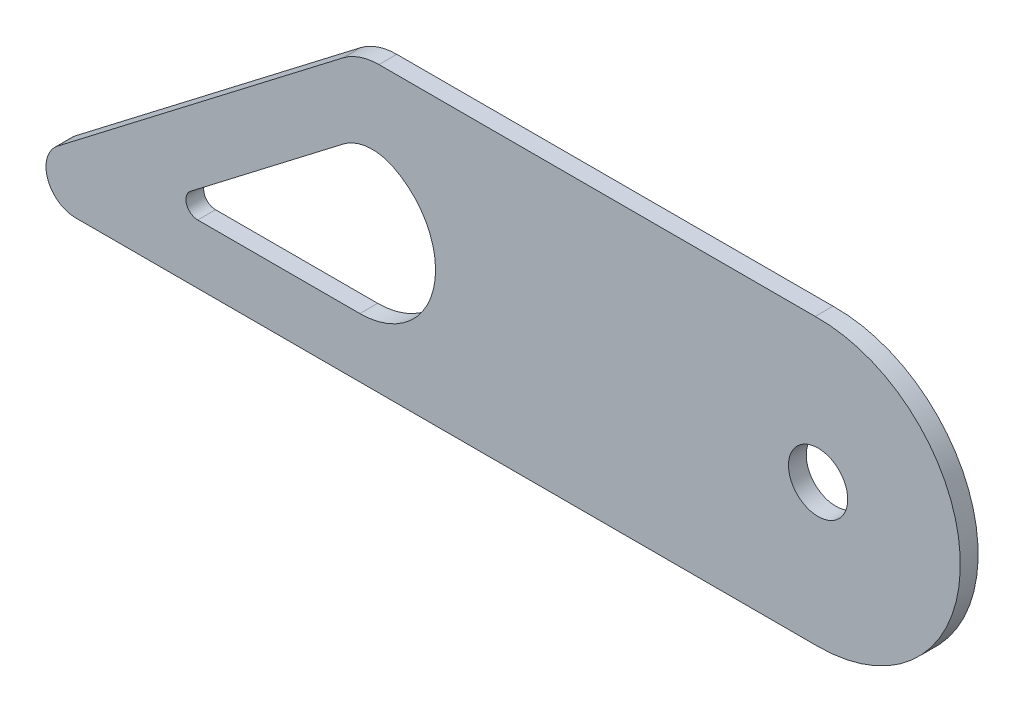
SolidWorks part; units mm, degrees
ref_plane "Front" through (0, 0, 0) normal (0, 0, 1) x (1, 0, 0)
ref_plane "Top" through (0, 0, 0) normal (0, 1, 0) x (1, 0, 0)
ref_plane "Right" through (0, 0, 0) normal (1, 0, 0) x (0, 0, -1)
sketch "Sketch2" plane through (0, 0, 0) normal (0, 0, 1) x (1, 0, 0)
  line L0 (-398.4685, -10.3406) -> (-639.1765, -195.1456)
  line L1 (0, 0) -> (-368.0198, 0)
  line L3 (2.433, -239.9753) -> (-623.9521, -239.9753)
  line L7 (-526.9809, -172.0434) -> (-398.0142, -73.0284)
  line L9 (-384.0981, -189.9753) -> (-520.8912, -189.9753)
  arc A0 (2.433, -239.9753) -> (0, 0) centre (2.433, -119.9753) ccw
  arc A1 (-623.9521, -239.9753) -> (-639.1765, -195.1456) centre (-623.9521, -214.9753) cw
  arc A4 (-368.0198, 0) -> (-398.4685, -10.3406) centre (-368.0198, -50) ccw
  arc A6 (-356.1154, -68.8066) -> (-384.0981, -189.9753) centre (-384.0981, -126.1598) cw
  arc A7 (-398.0142, -73.0284) -> (-356.1154, -68.8066) centre (-373.6552, -104.756) cw
  arc A8 (-526.9809, -172.0434) -> (-520.8912, -189.9753) centre (-520.8912, -179.9753) ccw
  circle A9 centre (2.433, -119.9753) radius 25
  point P0 (2.433, -119.9753)
  point P10 (-697.567, -239.9753)
  point P14 (-384.0981, -2.6557)
  point P20 (-385, 0)
  dimension "D3" = 120
  dimension "D4" = 25
  dimension "D7" = 40
  dimension "D8" = 50
  dimension "D9" = 10
  dimension "D10" = 386.5311
  dimension "D11" = 63.8155
  dimension "D12" = 50
  dimension "D1" = 385
  dimension "D2" = 700
  dimension "D5" = 50
  dimension "D6" = 50
extrude "Boss-Extrude1" add sketch "Sketch2" along normal mid plane 15
